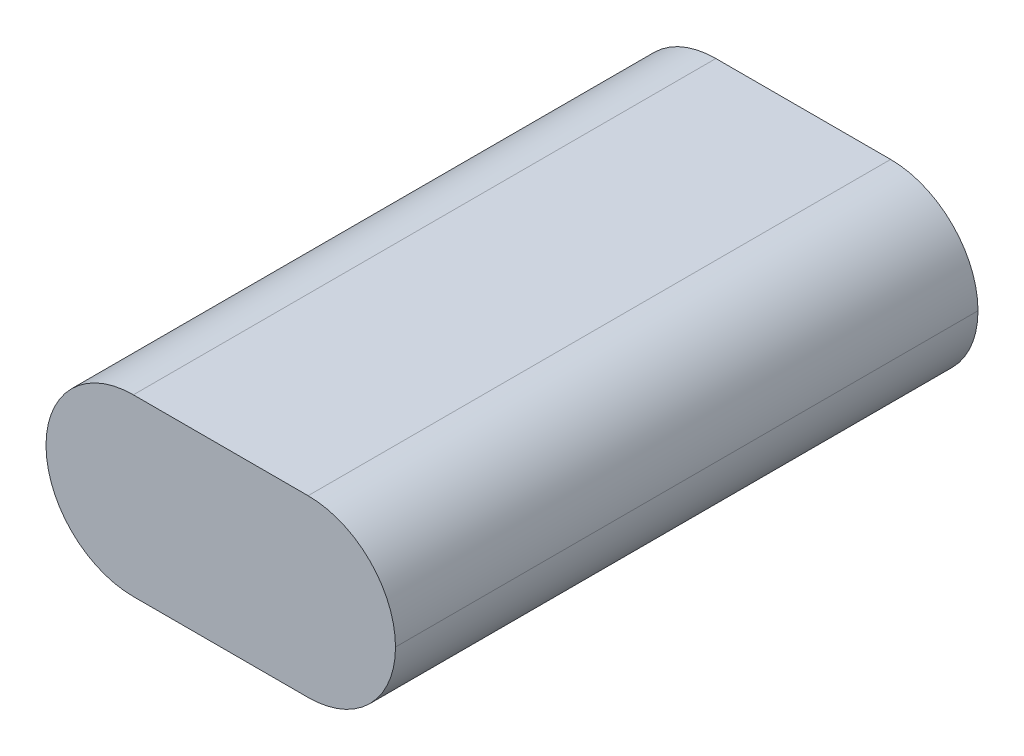
SolidWorks part; units mm, degrees
ref_plane "Front Plane" through (0, 0, 0) normal (0, 0, 1) x (1, 0, 0)
ref_plane "Top Plane" through (0, 0, 0) normal (0, 1, 0) x (1, 0, 0)
ref_plane "Right Plane" through (0, 0, 0) normal (1, 0, 0) x (0, 0, -1)
sketch "Sketch1" plane through (0, 0, 0) normal (0, 1, 0) x (1, 0, 0)
  line L1 (0, 0) -> (18, 0)
  line L2 (0, 0) -> (0, 30)
  line L3 (0, 30) -> (18, 30)
  line L4 (18, 0) -> (18, 30)
  dimension "D1" = 18
  dimension "D2" = 30
extrude "Boss-Extrude1" add sketch "Sketch1" along normal blind 9
sketch "Sketch2" plane through (0, 0, -30) normal (0, 0, -1) x (-1, 0, 0)
  line L0 (-18, 4.5) -> (0, 4.5) construction
  line L1 (-18, 9) -> (-18, 0) construction
  line L2 (0, 9) -> (0, 0) construction
  line L4 (-15.25, 7.05) -> (-2.75, 7.05)
  line L5 (-15.25, 7.05) -> (-15.25, 1.95)
  line L6 (-15.25, 1.95) -> (-2.75, 1.95)
  line L7 (-2.75, 7.05) -> (-2.75, 1.95)
  line L8 (-15.25, 7.05) -> (-2.75, 1.95) construction
  line L9 (-15.25, 1.95) -> (-2.75, 7.05) construction
  point P6 (-9, 4.5)
  dimension "D1" = 12.5
  dimension "D2" = 5.1
extrude "Cut-Extrude1" cut sketch "Sketch2" against normal blind 10
fillet "Fillet1" radius 4.5 4 edges at (0, 0, -15) (0, 9, -15) (18, 0, -15) (18, 9, -15)
